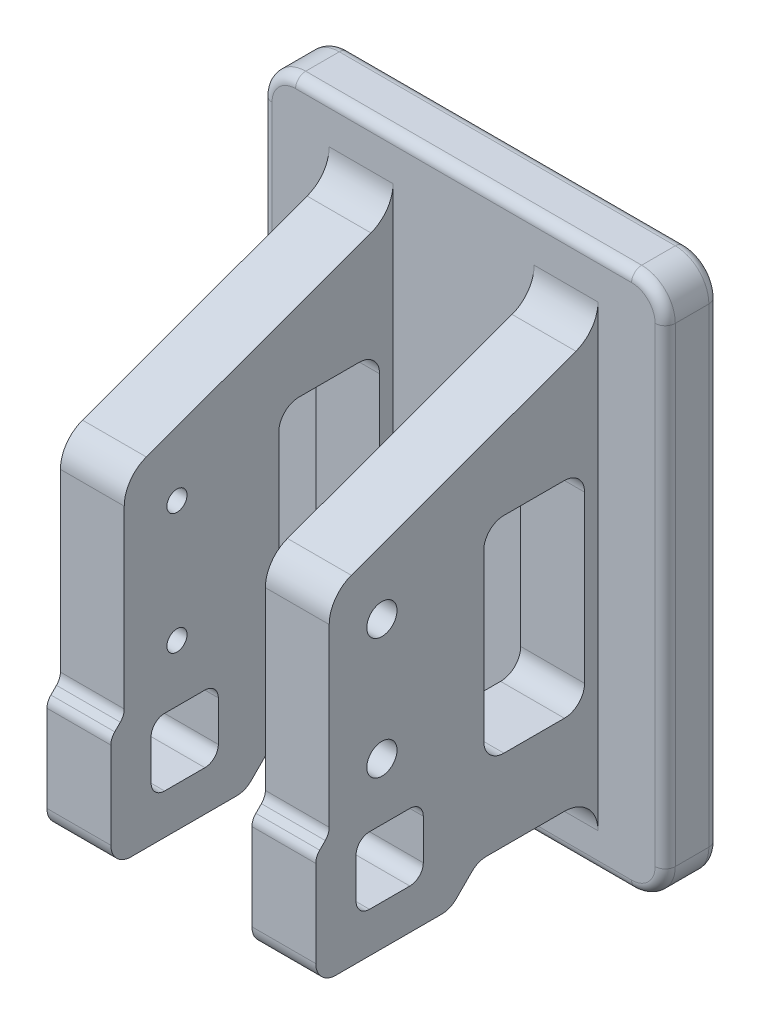
SolidWorks part; units mm, degrees
ref_plane "Front Plane" through (0, 0, 0) normal (0, 0, 1) x (1, 0, 0)
ref_plane "Top Plane" through (0, 0, 0) normal (0, 1, 0) x (1, 0, 0)
ref_plane "Right Plane" through (0, 0, 0) normal (1, 0, 0) x (0, 0, -1)
sketch "Sketch3" plane through (0, 0, 30) normal (0, 0, -1) x (-1, 0, 0)
  line L0 (95, 33.2573) -> (65, 33.2573) construction
  line L15 (80, 53.2573) -> (80, 33.2573) construction
  line L20 (55, 53.2573) -> (105, 53.2573)
  line L29 (55, -26.7427) -> (105, -26.7427)
  line L31 (110, -21.7427) -> (110, 48.2573)
  line L33 (50, -21.7427) -> (50, 48.2573)
  arc A17 (50, 48.2573) -> (55, 53.2573) centre (55, 48.2573) cw
  arc A18 (110, 48.2573) -> (105, 53.2573) centre (105, 48.2573) ccw
  arc A21 (50, -21.7427) -> (55, -26.7427) centre (55, -21.7427) ccw
  arc A22 (110, -21.7427) -> (105, -26.7427) centre (105, -21.7427) cw
  dimension "D1" = 5
extrude "Boss-Extrude1" add sketch "Sketch3" along normal blind 8
sketch "Sketch8" plane through (0, 0, 22) normal (0, 0, -1) x (-1, 0, 0)
  line L0 (50, 13.2573) -> (110, 13.2573) construction
  line L1 (50, 48.2573) -> (50, -21.7427) construction
  line L2 (110, -21.7427) -> (110, 48.2573) construction
  line L3 (80, 13.2573) -> (80, -26.7427) construction
  line L4 (55, -26.7427) -> (105, -26.7427) construction
  line L5 (78.25, 15.3786) -> (78.25, 11.136)
  line L6 (81.75, 15.3786) -> (81.75, 11.136)
  arc A0 (78.25, 11.136) -> (81.75, 11.136) centre (80, 13.2573) ccw
  arc A1 (81.75, 15.3786) -> (78.25, 15.3786) centre (80, 13.2573) ccw
extrude "Cut-Extrude3" cut sketch "Sketch8" against normal blind 3
sketch "Sketch10" plane through (0, 0, 22) normal (0, 0, -1) x (-1, 0, 0)
  line L0 (50, 13.2573) -> (110, 13.2573) construction
  line L1 (50, 48.2573) -> (50, -21.7427) construction
  line L2 (110, -21.7427) -> (110, 48.2573) construction
  line L3 (80, 13.2573) -> (80, -26.7427) construction
  line L4 (55, -26.7427) -> (105, -26.7427) construction
  line L7 (81.75, 11.136) -> (81.75, 15.3786)
  line L8 (78.25, 15.3786) -> (78.25, 11.136)
  line L9 (81.75, 11.136) -> (81.75, 15.3786)
  line L10 (78.25, 15.3786) -> (78.25, 11.136)
  circle A3 centre (80, 13.2573) radius 9.75
  arc A5 (78.25, 11.136) -> (81.75, 11.136) centre (80, 13.2573) ccw
  arc A6 (81.75, 15.3786) -> (78.25, 15.3786) centre (80, 13.2573) ccw
  arc A7 (78.25, 11.136) -> (81.75, 11.136) centre (80, 13.2573) ccw
  arc A8 (81.75, 15.3786) -> (78.25, 15.3786) centre (80, 13.2573) ccw
  dimension "D1" = 0
extrude "Boss-Extrude4" add sketch "Sketch10" along normal blind 9
fillet "Fillet2" radius 1.5 16 edges at (-80, -26.7427, 30) (-80, 53.2573, 30) (-50, 13.2573, 30) (-51.4645, 51.7928, 30) (-108.5355, 51.7928, 30) (-110, 13.2573, 30) (-80, -26.7427, 22) (-50, 13.2573, 22) (-51.4645, 51.7928, 22) (-80, 53.2573, 22) (-108.5355, 51.7928, 22) (-110, 13.2573, 22) (-108.5355, -25.2783, 22) (-51.4645, -25.2783, 22) (-108.5355, -25.2783, 30) (-51.4645, -25.2783, 30)
sketch "Sketch11" plane through (0, 0, 22) normal (0, 0, -1) x (-1, 0, 0)
  line L0 (50, 13.2573) -> (110, 13.2573) construction
  line L1 (50, -21.7427) -> (50, 48.2573) construction
  line L2 (110, 48.2573) -> (110, -21.7427) construction
  line L3 (80, 13.2573) -> (80, -26.7427) construction
  line L4 (105, -26.7427) -> (55, -26.7427) construction
  circle A0 centre (80, 13.2573) radius 11.75
extrude "Boss-Extrude5" add sketch "Sketch11" along normal blind 1
sketch "Sketch14" plane through (-70, 0, 0) normal (1, 0, 0) x (0, 0, -1)
  line L0 (-22, 1.5073) -> (-22, 25.0073) construction
  line L1 (-30, 48.2573) -> (-30, -21.7427) construction
  line L2 (-70, -1.7605) -> (-70, 28.6985)
  line L3 (-70, 28.6985) -> (-30, 43.2573)
  line L4 (-30, -16.3789) -> (-47.8764, -16.3789)
  line L6 (-30, -16.3789) -> (-30, 43.2573)
  line L7 (-47.8764, -16.3789) -> (-52, -20.5025)
  line L8 (-52, -20.5025) -> (-72, -20.5025)
  line L9 (-72, -20.5025) -> (-72, -3.7605)
  line L11 (-72, -3.7605) -> (-70, -1.7605)
  circle A6 centre (-62.1572, 3.9815) radius 1.5 construction
  circle A7 centre (-62.1572, 21.9815) radius 1.5 construction
  circle A8 centre (-62.1572, 3.9815) radius 1.5
  circle A9 centre (-62.1572, 21.9815) radius 1.5
extrude "Boss-Extrude7" add sketch "Sketch14" along normal blind 10
sketch "Sketch15" plane through (-90, 0, 0) normal (-1, 0, 0) x (0, 0, 1)
  line L4 (47.8764, -16.3789) -> (52, -20.5025)
  line L5 (70, -1.7605) -> (70, 28.6985)
  line L6 (70, 28.6985) -> (30, 43.2573)
  line L7 (30, 43.2573) -> (30, -16.3789)
  line L9 (70, -1.7605) -> (70, 28.6985)
  line L10 (70, 28.6985) -> (30, 43.2573)
  line L15 (30, 43.2573) -> (30, -16.3789)
  line L20 (47.8764, -16.3789) -> (52, -20.5025)
  line L21 (52, -20.5025) -> (72, -20.5025)
  line L22 (52, -20.5025) -> (72, -20.5025)
  line L23 (72, -20.5025) -> (72, -3.7605)
  line L24 (72, -20.5025) -> (72, -3.7605)
  line L25 (72, -3.7605) -> (70, -1.7605)
  line L26 (72, -3.7605) -> (70, -1.7605)
  line L27 (30, -16.3789) -> (47.8764, -16.3789)
  line L28 (30, -16.3789) -> (47.8764, -16.3789)
  circle A2 centre (62.1572, 3.9815) radius 1.5 construction
  circle A3 centre (62.1572, 21.9815) radius 1.5 construction
  circle A4 centre (62.1572, 3.9815) radius 1.5
  circle A5 centre (62.1572, 21.9815) radius 1.5
  dimension "D1" = 0
extrude "Boss-Extrude8" add sketch "Sketch15" along normal blind 10
fillet "Fillet3" radius 5 6 edges at (-65, 43.2573, 30) (-95, 43.2573, 30) (-95, 28.6985, 70) (-65, 28.6985, 70) (-95, -16.3789, 30) (-65, -16.3789, 30)
fillet "Fillet4" radius 3 6 edges at (-95, -20.5025, 72) (-65, -20.5025, 72) (-65, -20.5025, 52) (-95, -20.5025, 52) (-95, -16.3789, 47.8764) (-65, -16.3789, 47.8764)
sketch "Sketch16" plane through (-90, 0, 0) normal (1, 0, 0) x (0, 0, -1)
  line L8 (-72, -3.7605) -> (-72, -17.5025)
  line L9 (-69, -20.5025) -> (-53.2426, -20.5025)
  line L10 (-51.1213, -19.6238) -> (-48.7551, -17.2576)
  line L11 (-46.6337, -16.3789) -> (-35, -16.3789)
  line L12 (-30, -21.3789) -> (-30, 46.7583)
  line L13 (-33.2899, 42.0599) -> (-66.7101, 29.8959)
  line L14 (-70, 25.1974) -> (-70, -1.7605)
  line L15 (-70, -1.7605) -> (-72, -3.7605)
  line L16 (-72, -3.7605) -> (-72, -17.5025)
  line L17 (-69, -20.5025) -> (-53.2426, -20.5025)
  line L18 (-51.1213, -19.6238) -> (-48.7551, -17.2576)
  line L19 (-46.6337, -16.3789) -> (-35, -16.3789)
  line L20 (-30, -21.3789) -> (-30, 46.7583)
  line L21 (-33.2899, 42.0599) -> (-66.7101, 29.8959)
  line L22 (-70, 25.1974) -> (-70, -1.7605)
  line L23 (-70, -1.7605) -> (-72, -3.7605)
  arc A6 (-72, -17.5025) -> (-69, -20.5025) centre (-69, -17.5025) ccw
  arc A7 (-53.2426, -20.5025) -> (-51.1213, -19.6238) centre (-53.2426, -17.5025) ccw
  arc A8 (-46.6337, -16.3789) -> (-48.7551, -17.2576) centre (-46.6337, -19.3789) ccw
  arc A9 (-30, -21.3789) -> (-35, -16.3789) centre (-35, -21.3789) ccw
  arc A10 (-33.2899, 42.0599) -> (-30, 46.7583) centre (-35, 46.7583) ccw
  arc A11 (-66.7101, 29.8959) -> (-70, 25.1974) centre (-65, 25.1974) ccw
  arc A12 (-72, -17.5025) -> (-69, -20.5025) centre (-69, -17.5025) ccw
  arc A13 (-53.2426, -20.5025) -> (-51.1213, -19.6238) centre (-53.2426, -17.5025) ccw
  arc A14 (-46.6337, -16.3789) -> (-48.7551, -17.2576) centre (-46.6337, -19.3789) ccw
  arc A15 (-30, -21.3789) -> (-35, -16.3789) centre (-35, -21.3789) ccw
  arc A16 (-33.2899, 42.0599) -> (-30, 46.7583) centre (-35, 46.7583) ccw
  arc A17 (-66.7101, 29.8959) -> (-70, 25.1974) centre (-65, 25.1974) ccw
  dimension "D1" = 0
extrude "Cut-Extrude4" cut sketch "Sketch16" against normal blind 0.25
sketch "Sketch17" plane through (-70, 0, 0) normal (-1, 0, 0) x (0, 0, 1)
  line L8 (53.2426, -20.5025) -> (69, -20.5025)
  line L9 (72, -17.5025) -> (72, -3.7605)
  line L10 (72, -3.7605) -> (70, -1.7605)
  line L11 (70, -1.7605) -> (70, 25.1974)
  line L12 (66.7101, 29.8959) -> (33.2899, 42.0599)
  line L13 (30, 46.7583) -> (30, -21.3789)
  line L14 (35, -16.3789) -> (46.6337, -16.3789)
  line L15 (48.7551, -17.2576) -> (51.1213, -19.6238)
  line L16 (53.2426, -20.5025) -> (69, -20.5025)
  line L17 (72, -17.5025) -> (72, -3.7605)
  line L18 (72, -3.7605) -> (70, -1.7605)
  line L19 (70, -1.7605) -> (70, 25.1974)
  line L20 (66.7101, 29.8959) -> (33.2899, 42.0599)
  line L21 (30, 46.7583) -> (30, -21.3789)
  line L22 (35, -16.3789) -> (46.6337, -16.3789)
  line L23 (48.7551, -17.2576) -> (51.1213, -19.6238)
  arc A6 (69, -20.5025) -> (72, -17.5025) centre (69, -17.5025) ccw
  arc A7 (70, 25.1974) -> (66.7101, 29.8959) centre (65, 25.1974) ccw
  arc A8 (30, 46.7583) -> (33.2899, 42.0599) centre (35, 46.7583) ccw
  arc A9 (35, -16.3789) -> (30, -21.3789) centre (35, -21.3789) ccw
  arc A10 (48.7551, -17.2576) -> (46.6337, -16.3789) centre (46.6337, -19.3789) ccw
  arc A11 (51.1213, -19.6238) -> (53.2426, -20.5025) centre (53.2426, -17.5025) ccw
  arc A12 (69, -20.5025) -> (72, -17.5025) centre (69, -17.5025) ccw
  arc A13 (70, 25.1974) -> (66.7101, 29.8959) centre (65, 25.1974) ccw
  arc A14 (30, 46.7583) -> (33.2899, 42.0599) centre (35, 46.7583) ccw
  arc A15 (35, -16.3789) -> (30, -21.3789) centre (35, -21.3789) ccw
  arc A16 (48.7551, -17.2576) -> (46.6337, -16.3789) centre (46.6337, -19.3789) ccw
  arc A17 (51.1213, -19.6238) -> (53.2426, -20.5025) centre (53.2426, -17.5025) ccw
  dimension "D1" = 0
extrude "Cut-Extrude5" cut sketch "Sketch17" against normal blind 0.25
sketch "Sketch18" plane through (-100, 0, 0) normal (-1, 0, 0) x (0, 0, 1)
  line L0 (23.5, 53.2573) -> (28.5, 53.2573) construction
  line L1 (35, 26.2573) -> (44, 26.2573)
  line L2 (32, 23.2573) -> (32, -1.3789)
  line L3 (35, -4.3789) -> (44, -4.3789)
  line L4 (47, 23.2573) -> (47, -1.3789)
  line L5 (35, -16.3789) -> (46.6337, -16.3789) construction
  line L6 (30, 48.2573) -> (30, -21.7427) construction
  line L7 (53.2426, -20.5025) -> (69, -20.5025) construction
  line L8 (64, -14.5025) -> (58, -14.5025)
  line L9 (66, -12.5025) -> (66, -6.5025)
  line L10 (64, -4.5025) -> (58, -4.5025)
  line L11 (56, -12.5025) -> (56, -6.5025)
  line L12 (72, -17.5025) -> (72, -3.7605) construction
  arc A0 (44, -4.3789) -> (47, -1.3789) centre (44, -1.3789) ccw
  arc A1 (32, -1.3789) -> (35, -4.3789) centre (35, -1.3789) ccw
  arc A2 (35, 26.2573) -> (32, 23.2573) centre (35, 23.2573) ccw
  arc A3 (44, 26.2573) -> (47, 23.2573) centre (44, 23.2573) cw
  arc A4 (66, -6.5025) -> (64, -4.5025) centre (64, -6.5025) ccw
  arc A5 (64, -14.5025) -> (66, -12.5025) centre (64, -12.5025) ccw
  arc A6 (58, -14.5025) -> (56, -12.5025) centre (58, -12.5025) cw
  arc A7 (58, -4.5025) -> (56, -6.5025) centre (58, -6.5025) ccw
  point P16 (32, 26.2573)
  point P19 (47, 26.2573)
  point P30 (66, -4.5025)
  point P33 (66, -14.5025)
  point P38 (56, -4.5025)
  dimension "D5" = 3
  dimension "D10" = 2
  dimension "D1" = 27
  dimension "D2" = 12
  dimension "D3" = 15
  dimension "D4" = 2
  dimension "D6" = 6
  dimension "D7" = 6
  dimension "D8" = 10
  dimension "D9" = 10
extrude "Cut-Extrude6" cut sketch "Sketch18" against normal up to surface (40 mm away) up to face at (-60, -0.7658, 53.3813)
sketch "Sketch19" plane through (-60, 0, 0) normal (1, 0, 0) x (0, 0, -1)
  circle A0 centre (-62.1572, 21.9815) radius 2.25
  circle A1 centre (-62.1572, 3.9815) radius 2.25
extrude "Cut-Extrude7" cut sketch "Sketch19" against normal blind 4
chamfer "Chamfer1" distance 1.5 angle 45 2 edges at (-100, 2.4815, 62.1572) (-100, 20.4815, 62.1572)
sketch "Sketch20" plane through (0, 0, 72) normal (0, 0, 1) x (1, 0, 0)
  line L0 (-105, 53.2573) -> (-55, 53.2573) construction
  line L1 (-90.5, 53.2573) -> (-69.5, 53.2573)
  line L2 (-90.5, 53.2573) -> (-90.5, -26.7427)
  line L3 (-90.5, -26.7427) -> (-69.5, -26.7427)
  line L4 (-69.5, 53.2573) -> (-69.5, -26.7427)
  line L5 (-55, -26.7427) -> (-105, -26.7427) construction
  line L6 (-69.75, 46.7583) -> (-69.75, 42.0599) construction
  line L7 (-90.25, 42.0599) -> (-90.25, 29.8959) construction
  dimension "D1" = 0.25
  dimension "D2" = 0.25
extrude "Cut-Extrude8" cut sketch "Sketch20" against normal up to surface (42 mm away) up to face at (-95.125, 12.6897, 30)
fillet "Fillet5" radius 2 4 edges at (-95.25, -3.7605, 72) (-95.25, -1.7605, 70) (-64.75, -3.7605, 72) (-64.75, -1.7605, 70)
sketch "Sketch21" plane through (0, 0, 21) normal (0, 0, -1) x (-1, 0, 0)
  line L2 (81.75, 11.136) -> (81.75, 15.3786)
  line L3 (78.25, 15.3786) -> (78.25, 11.136)
  line L4 (81.75, 11.136) -> (81.75, 15.3786)
  line L5 (78.25, 15.3786) -> (78.25, 11.136)
  arc A2 (81.75, 15.3786) -> (78.25, 15.3786) centre (80, 13.2573) ccw
  arc A3 (78.25, 11.136) -> (81.75, 11.136) centre (80, 13.2573) ccw
  arc A4 (81.75, 15.3786) -> (78.25, 15.3786) centre (80, 13.2573) ccw
  arc A5 (78.25, 11.136) -> (81.75, 11.136) centre (80, 13.2573) ccw
  dimension "D1" = 0
extrude "Cut-Extrude9" cut sketch "Sketch21" against normal blind 5
